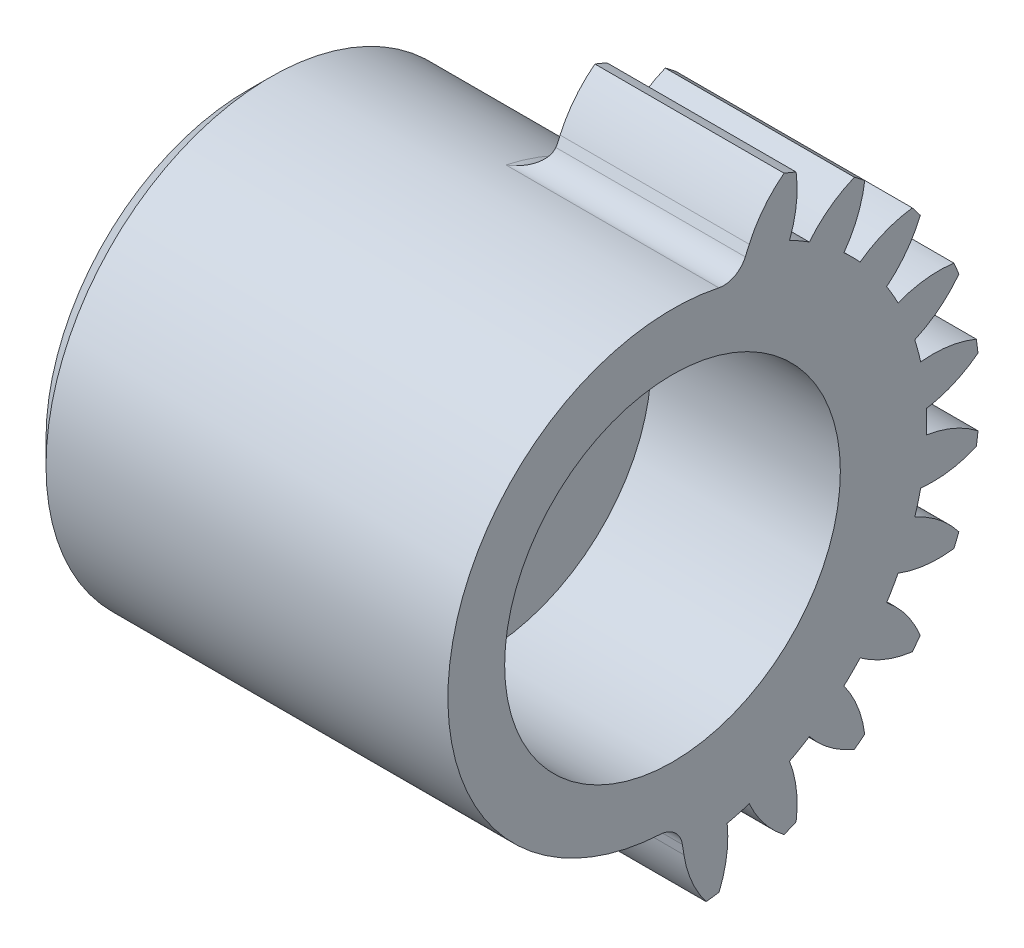
SolidWorks part; units mm, degrees
ref_plane "Plane1" through (0, 0, 0) normal (0, 0, 1) x (1, 0, 0)
ref_plane "Plane2" through (0, 0, 0) normal (0, 1, 0) x (1, 0, 0)
ref_plane "Plane3" through (0, 0, 0) normal (1, 0, 0) x (0, 0, -1)
sketch "HoldingSke" plane through (0, 0, 0) normal (0, 1, 0) x (1, 0, 0)
  line L0 (0, 0) -> (0.9135, -0.4067)
  line L1 (-15, 0) -> (100, 0) construction
  line L2 (0, 0) -> (-2.1039, 2.3779)
  line L3 (0, 0) -> (-11.863, 4.5341)
  line L4 (0, 0) -> (7.8894, 3.5126)
  line L5 (0, 0) -> (-46.8476, -17.4728)
  line L6 (0, 0) -> (-6.6317, -4.4744)
  line L7 (-2.1039, 2.3779) -> (8.6586, 51.2059)
  line L8 (-76.2, 54.61) -> (-75.3, 54.61)
  line L9 (-71.009, 38.7566) -> (-53.1078, 45.2721)
  line L10 (-76.2, 71.12) -> (104.1128, 71.12)
  line L11 (0, 0) -> (-8, 0)
  line L12 (-76.2, 101.6) -> (-76.162, 101.6)
  line L13 (24.9733, 27.94) -> (52.9518, 28.4284)
  line L14 (24.9733, 27.94) -> (24.9743, 27.94)
  line L15 (24.9733, 27.94) -> (100.4006, 29.5858)
  line L16 (-63.627, -1) -> (-12.827, -1)
  circle A0 centre (0, 0) radius 2.5
  circle A1 centre (0, 0) radius 10.749
  circle A2 centre (0, 0) radius 37.5
  circle A3 centre (0, 0) radius 2.5
  dimension "Num_teeth" = 24
  dimension "Pitch_radius" = 180.3128
  dimension "Width" = 8
  dimension "Thickness" = 8
sketch "BasProSke" plane through (0, 0, 0) normal (0, 1, 0) x (1, 0, 0)
  line L0 (-10, 0) -> (60, 0) construction
  line L1 (0, 0) -> (0, 13)
  line L2 (0, 0) -> (8, 0)
  line L3 (8, 0) -> (8, 13)
  line L4 (8, 13) -> (0, 13)
  dimension "Thickness" = 8
  dimension "Diameter" = 26
revolve "Base-Revolve" add sketch "BasProSke" angle 360 about L0
sketch "TooCutSke" plane through (0, 0, 0) normal (1, 0, 0) x (0, 0, -1)
  line L1 (0, 0) -> (0, 107) construction
  line L2 (0, 0) -> (-0.8513, 11.9698) construction
  line L3 (0, 0) -> (-3.127, 23.752) construction
  line L4 (-0.8513, 11.9698) -> (-1.5635, 11.876) construction
  arc A0 (0.4834, 10.7381) -> (-0.4834, 10.7381) centre (0, 0) ccw
  arc A1 (1.4409, 12.9455) -> (-1.4409, 12.9455) centre (0, 0) ccw
  circle A2 centre (0, 0) radius 12 construction
  circle A3 centre (0, 0) radius 11.2763 construction
  arc A4 (-0.4834, 10.7381) -> (-1.4409, 12.9455) centre (-5.2252, 9.9926) ccw
  arc A5 (1.4409, 12.9455) -> (0.4834, 10.7381) centre (5.2252, 9.9926) ccw
extrude "ToothCut" cut sketch "TooCutSke" along normal through all
fillet "Breaks" [suppressed] radius 0.02 tangent propagation no
fillet "RootFillets" [suppressed] radius 0.251
pattern_circular "TeethCuts" count 24 every 15 about axis through (-10, 0, 0) along (1, 0, 0) of "ToothCut", "RootFillets", "Breaks"
sketch "HubNeaOneSke" plane through (0, 0, 0) normal (-1, 0, 0) x (0, 0, 1)
  circle A0 centre (0, 0) radius 10.749
  dimension "Diameter" = 21.498
extrude "HubNearOne" [suppressed] add sketch "HubNeaOneSke" along normal blind 42.0001
sketch "HubNeaBotSke" plane through (0, 0, 0) normal (-1, 0, 0) x (0, 0, 1)
  circle A0 centre (0, 0) radius 10.749
  dimension "Diameter" = 21.498
extrude "HubNearBoth" [suppressed] add sketch "HubNeaBotSke" along normal blind 21
ref_plane "FarPln" through (8, 0, 0) normal (1, 0, 0) x (0, 0, -1)
sketch "HubFarSke" plane through (8, 0, 0) normal (1, 0, 0) x (0, 0, -1)
  circle A0 centre (0, 0) radius 10.749
  dimension "Diameter" = 21.498
extrude "HubFar" [suppressed] add sketch "HubFarSke" along normal blind 21
sketch "BorSke" plane through (0, 0, 0) normal (1, 0, 0) x (0, 0, -1)
  circle A0 centre (0, 0) radius 2.5
  dimension "Diameter" = 5
extrude "Bore" cut sketch "BorSke" along normal mid plane 100.0001
sketch "KeySke" plane through (0, 0, 0) normal (1, 0, 0) x (0, 0, -1)
  line L0 (-1, 0) -> (-1, 3.4)
  line L1 (-1, 3.4) -> (1, 3.4)
  line L2 (1, 3.4) -> (1, 0)
  line L3 (0, 0) -> (0, 34) construction
  line L4 (-1, 0) -> (1, 0)
  dimension "Width" = 2
extrude "Keyway" [suppressed] cut sketch "KeySke" along normal mid plane 100.0001
pattern_circular "Keyway2" [suppressed] count 2 every 90 about axis through (-10, 0, 0) along (1, 0, 0)
sketch "Sketch2" plane through (0, 0, 0) normal (-1, 0, 0) x (0, 0, 1)
  line L0 (-3.2462, 10.2471) -> (-2.7359, 9.0975)
  line L1 (-0.4834, -10.7381) -> (-0.2881, -9.4956)
  circle A0 centre (0, 0) radius 2.5 construction
  circle A1 centre (0, 0) radius 2.5
  circle A2 centre (0, 0) radius 9.5
  circle A3 centre (0, 0) radius 7.1
  arc A100 (10.7381, 0.4834) -> (12.9219, 1.4227) centre (9.9926, 5.2252) ccw
  arc A101 (12.9219, 1.4227) -> (12.8498, 1.9702) centre (0, 0) ccw
  arc A102 (12.8498, 1.9702) -> (10.4974, 2.3123) centre (11.0045, -2.4609) ccw
  arc A103 (10.4974, 2.3123) -> (10.2471, 3.2462) centre (0, 0) ccw
  arc A104 (10.2471, 3.2462) -> (12.1134, 4.7186) centre (8.2997, 7.6334) ccw
  arc A105 (12.1134, 4.7186) -> (11.902, 5.2289) centre (0, 0) ccw
  arc A106 (11.902, 5.2289) -> (9.5412, 4.9504) centre (11.2665, 0.4712) ccw
  arc A107 (9.5412, 4.9504) -> (9.0578, 5.7877) centre (0, 0) ccw
  arc A108 (9.0578, 5.7877) -> (10.4794, 7.693) centre (6.0413, 9.5215) ccw
  arc A109 (10.4794, 7.693) -> (10.1432, 8.1312) centre (0, 0) ccw
  arc A110 (10.1432, 8.1312) -> (7.9348, 7.2511) centre (10.7606, 3.3711) ccw
  arc A111 (7.9348, 7.2511) -> (7.2511, 7.9348) centre (0, 0) ccw
  arc A112 (7.2511, 7.9348) -> (8.1312, 10.1432) centre (3.3711, 10.7606) ccw
  arc A113 (8.1312, 10.1432) -> (7.693, 10.4794) centre (0, 0) ccw
  arc A114 (7.693, 10.4794) -> (5.7877, 9.0578) centre (9.5215, 6.0413) ccw
  arc A115 (5.7877, 9.0578) -> (4.9504, 9.5412) centre (0, 0) ccw
  arc A116 (4.9504, 9.5412) -> (5.2289, 11.902) centre (0.4712, 11.2665) ccw
  arc A117 (5.2289, 11.902) -> (4.7186, 12.1134) centre (0, 0) ccw
  arc A118 (4.7186, 12.1134) -> (3.2462, 10.2471) centre (7.6334, 8.2997) ccw
  arc A119 (3.2462, 10.2471) -> (2.3123, 10.4974) centre (0, 0) ccw
  arc A120 (2.3123, 10.4974) -> (1.9702, 12.8498) centre (-2.4609, 11.0045) ccw
  arc A121 (1.9702, 12.8498) -> (1.4227, 12.9219) centre (0, 0) ccw
  arc A122 (1.4227, 12.9219) -> (0.4834, 10.7381) centre (5.2252, 9.9926) ccw
  arc A123 (0.4834, 10.7381) -> (-0.4834, 10.7381) centre (0, 0) ccw
  arc A124 (-0.4834, 10.7381) -> (-1.4227, 12.9219) centre (-5.2252, 9.9926) ccw
  arc A125 (-1.4227, 12.9219) -> (-1.9702, 12.8498) centre (0, 0) ccw
  arc A126 (-1.9702, 12.8498) -> (-2.3123, 10.4974) centre (2.4609, 11.0045) ccw
  arc A127 (-2.3123, 10.4974) -> (-3.2462, 10.2471) centre (0, 0) ccw
  arc A128 (-3.2462, 10.2471) -> (-4.7186, 12.1134) centre (-7.6334, 8.2997) ccw
  arc A129 (-4.7186, 12.1134) -> (-5.2289, 11.902) centre (0, 0) ccw
  arc A130 (-5.2289, 11.902) -> (-4.9504, 9.5412) centre (-0.4712, 11.2665) ccw
  arc A131 (-4.9504, 9.5412) -> (-5.7877, 9.0578) centre (0, 0) ccw
  arc A132 (-5.7877, 9.0578) -> (-7.693, 10.4794) centre (-9.5215, 6.0413) ccw
  arc A133 (-7.693, 10.4794) -> (-8.1312, 10.1432) centre (0, 0) ccw
  arc A134 (-8.1312, 10.1432) -> (-7.2511, 7.9348) centre (-3.3711, 10.7606) ccw
  arc A135 (-7.2511, 7.9348) -> (-7.9348, 7.2511) centre (0, 0) ccw
  arc A136 (-7.9348, 7.2511) -> (-10.1432, 8.1312) centre (-10.7606, 3.3711) ccw
  arc A137 (-10.1432, 8.1312) -> (-10.4794, 7.693) centre (0, 0) ccw
  arc A138 (-10.4794, 7.693) -> (-9.0578, 5.7877) centre (-6.0413, 9.5215) ccw
  arc A139 (-9.0578, 5.7877) -> (-9.5412, 4.9504) centre (0, 0) ccw
  arc A140 (-9.5412, 4.9504) -> (-11.902, 5.2289) centre (-11.2665, 0.4712) ccw
  arc A141 (-11.902, 5.2289) -> (-12.1134, 4.7186) centre (0, 0) ccw
  arc A142 (-12.1134, 4.7186) -> (-10.2471, 3.2462) centre (-8.2997, 7.6334) ccw
  arc A143 (-10.2471, 3.2462) -> (-10.4974, 2.3123) centre (0, 0) ccw
  arc A144 (-10.4974, 2.3123) -> (-12.8498, 1.9702) centre (-11.0045, -2.4609) ccw
  arc A145 (-12.8498, 1.9702) -> (-12.9219, 1.4227) centre (0, 0) ccw
  arc A146 (-12.9219, 1.4227) -> (-10.7381, 0.4834) centre (-9.9926, 5.2252) ccw
  arc A147 (-10.7381, 0.4834) -> (-10.7381, -0.4834) centre (0, 0) ccw
  arc A148 (-10.7381, -0.4834) -> (-12.9219, -1.4227) centre (-9.9926, -5.2252) ccw
  arc A149 (-12.9219, -1.4227) -> (-12.8498, -1.9702) centre (0, 0) ccw
  arc A150 (-12.8498, -1.9702) -> (-10.4974, -2.3123) centre (-11.0045, 2.4609) ccw
  arc A151 (-10.4974, -2.3123) -> (-10.2471, -3.2462) centre (0, 0) ccw
  arc A152 (-10.2471, -3.2462) -> (-12.1134, -4.7186) centre (-8.2997, -7.6334) ccw
  arc A153 (-12.1134, -4.7186) -> (-11.902, -5.2289) centre (0, 0) ccw
  arc A154 (-11.902, -5.2289) -> (-9.5412, -4.9504) centre (-11.2665, -0.4712) ccw
  arc A155 (-9.5412, -4.9504) -> (-9.0578, -5.7877) centre (0, 0) ccw
  arc A156 (-9.0578, -5.7877) -> (-10.4794, -7.693) centre (-6.0413, -9.5215) ccw
  arc A157 (-10.4794, -7.693) -> (-10.1432, -8.1312) centre (0, 0) ccw
  arc A158 (-10.1432, -8.1312) -> (-7.9348, -7.2511) centre (-10.7606, -3.3711) ccw
  arc A159 (-7.9348, -7.2511) -> (-7.2511, -7.9348) centre (0, 0) ccw
  arc A160 (-7.2511, -7.9348) -> (-8.1312, -10.1432) centre (-3.3711, -10.7606) ccw
  arc A161 (-8.1312, -10.1432) -> (-7.693, -10.4794) centre (0, 0) ccw
  arc A162 (-7.693, -10.4794) -> (-5.7877, -9.0578) centre (-9.5215, -6.0413) ccw
  arc A163 (-5.7877, -9.0578) -> (-4.9504, -9.5412) centre (0, 0) ccw
  arc A164 (-4.9504, -9.5412) -> (-5.2289, -11.902) centre (-0.4712, -11.2665) ccw
  arc A165 (-5.2289, -11.902) -> (-4.7186, -12.1134) centre (0, 0) ccw
  arc A166 (-4.7186, -12.1134) -> (-3.2462, -10.2471) centre (-7.6334, -8.2997) ccw
  arc A167 (-3.2462, -10.2471) -> (-2.3123, -10.4974) centre (0, 0) ccw
  arc A168 (-2.3123, -10.4974) -> (-1.9702, -12.8498) centre (2.4609, -11.0045) ccw
  arc A169 (-1.9702, -12.8498) -> (-1.4227, -12.9219) centre (0, 0) ccw
  arc A170 (-1.4227, -12.9219) -> (-0.4834, -10.7381) centre (-5.2252, -9.9926) ccw
  arc A171 (-0.4834, -10.7381) -> (0.4834, -10.7381) centre (0, 0) ccw
  arc A172 (0.4834, -10.7381) -> (1.4227, -12.9219) centre (5.2252, -9.9926) ccw
  arc A173 (1.4227, -12.9219) -> (1.9702, -12.8498) centre (0, 0) ccw
  arc A174 (1.9702, -12.8498) -> (2.3123, -10.4974) centre (-2.4609, -11.0045) ccw
  arc A175 (2.3123, -10.4974) -> (3.2462, -10.2471) centre (0, 0) ccw
  arc A176 (3.2462, -10.2471) -> (4.7186, -12.1134) centre (7.6334, -8.2997) ccw
  arc A177 (4.7186, -12.1134) -> (5.2289, -11.902) centre (0, 0) ccw
  arc A178 (5.2289, -11.902) -> (4.9504, -9.5412) centre (0.4712, -11.2665) ccw
  arc A179 (4.9504, -9.5412) -> (5.7877, -9.0578) centre (0, 0) ccw
  arc A180 (5.7877, -9.0578) -> (7.693, -10.4794) centre (9.5215, -6.0413) ccw
  arc A181 (7.693, -10.4794) -> (8.1312, -10.1432) centre (0, 0) ccw
  arc A182 (8.1312, -10.1432) -> (7.2511, -7.9348) centre (3.3711, -10.7606) ccw
  arc A183 (7.2511, -7.9348) -> (7.9348, -7.2511) centre (0, 0) ccw
  arc A184 (7.9348, -7.2511) -> (10.1432, -8.1312) centre (10.7606, -3.3711) ccw
  arc A185 (10.1432, -8.1312) -> (10.4794, -7.693) centre (0, 0) ccw
  arc A186 (10.4794, -7.693) -> (9.0578, -5.7877) centre (6.0413, -9.5215) ccw
  arc A187 (9.0578, -5.7877) -> (9.5412, -4.9504) centre (0, 0) ccw
  arc A188 (9.5412, -4.9504) -> (11.902, -5.2289) centre (11.2665, -0.4712) ccw
  arc A189 (11.902, -5.2289) -> (12.1134, -4.7186) centre (0, 0) ccw
  arc A190 (12.1134, -4.7186) -> (10.2471, -3.2462) centre (8.2997, -7.6334) ccw
  arc A191 (10.2471, -3.2462) -> (10.4974, -2.3123) centre (0, 0) ccw
  arc A192 (10.4974, -2.3123) -> (12.8498, -1.9702) centre (11.0045, 2.4609) ccw
  arc A193 (12.8498, -1.9702) -> (12.9219, -1.4227) centre (0, 0) ccw
  arc A194 (12.9219, -1.4227) -> (10.7381, -0.4834) centre (9.9926, -5.2252) ccw
  arc A195 (10.7381, -0.4834) -> (10.7381, 0.4834) centre (0, 0) ccw
  arc A196 (10.7381, 0.4834) -> (12.9219, 1.4227) centre (9.9926, 5.2252) ccw
  arc A197 (12.9219, 1.4227) -> (12.8498, 1.9702) centre (0, 0) ccw
  arc A198 (12.8498, 1.9702) -> (10.4974, 2.3123) centre (11.0045, -2.4609) ccw
  arc A199 (10.4974, 2.3123) -> (10.2471, 3.2462) centre (0, 0) ccw
  arc A200 (10.2471, 3.2462) -> (12.1134, 4.7186) centre (8.2997, 7.6334) ccw
  arc A201 (12.1134, 4.7186) -> (11.902, 5.2289) centre (0, 0) ccw
  arc A202 (11.902, 5.2289) -> (9.5412, 4.9504) centre (11.2665, 0.4712) ccw
  arc A203 (9.5412, 4.9504) -> (9.0578, 5.7877) centre (0, 0) ccw
  arc A204 (9.0578, 5.7877) -> (10.4794, 7.693) centre (6.0413, 9.5215) ccw
  arc A205 (10.4794, 7.693) -> (10.1432, 8.1312) centre (0, 0) ccw
  arc A206 (10.1432, 8.1312) -> (7.9348, 7.2511) centre (10.7606, 3.3711) ccw
  arc A207 (7.9348, 7.2511) -> (7.2511, 7.9348) centre (0, 0) ccw
  arc A208 (7.2511, 7.9348) -> (8.1312, 10.1432) centre (3.3711, 10.7606) ccw
  arc A209 (8.1312, 10.1432) -> (7.693, 10.4794) centre (0, 0) ccw
  arc A210 (7.693, 10.4794) -> (5.7877, 9.0578) centre (9.5215, 6.0413) ccw
  arc A211 (5.7877, 9.0578) -> (4.9504, 9.5412) centre (0, 0) ccw
  arc A212 (4.9504, 9.5412) -> (5.2289, 11.902) centre (0.4712, 11.2665) ccw
  arc A213 (5.2289, 11.902) -> (4.7186, 12.1134) centre (0, 0) ccw
  arc A214 (4.7186, 12.1134) -> (3.2462, 10.2471) centre (7.6334, 8.2997) ccw
  arc A215 (3.2462, 10.2471) -> (2.3123, 10.4974) centre (0, 0) ccw
  arc A216 (2.3123, 10.4974) -> (1.9702, 12.8498) centre (-2.4609, 11.0045) ccw
  arc A217 (1.9702, 12.8498) -> (1.4227, 12.9219) centre (0, 0) ccw
  arc A218 (1.4227, 12.9219) -> (0.4834, 10.7381) centre (5.2252, 9.9926) ccw
  arc A219 (0.4834, 10.7381) -> (-0.4834, 10.7381) centre (0, 0) ccw
  arc A220 (-0.4834, 10.7381) -> (-1.4227, 12.9219) centre (-5.2252, 9.9926) ccw
  arc A221 (-1.4227, 12.9219) -> (-1.9702, 12.8498) centre (0, 0) ccw
  arc A222 (-1.9702, 12.8498) -> (-2.3123, 10.4974) centre (2.4609, 11.0045) ccw
  arc A223 (-2.3123, 10.4974) -> (-3.2462, 10.2471) centre (0, 0) ccw
  arc A224 (-3.2462, 10.2471) -> (-4.7186, 12.1134) centre (-7.6334, 8.2997) ccw
  arc A225 (-4.7186, 12.1134) -> (-5.2289, 11.902) centre (0, 0) ccw
  arc A226 (-5.2289, 11.902) -> (-4.9504, 9.5412) centre (-0.4712, 11.2665) ccw
  arc A227 (-4.9504, 9.5412) -> (-5.7877, 9.0578) centre (0, 0) ccw
  arc A228 (-5.7877, 9.0578) -> (-7.693, 10.4794) centre (-9.5215, 6.0413) ccw
  arc A229 (-7.693, 10.4794) -> (-8.1312, 10.1432) centre (0, 0) ccw
  arc A230 (-8.1312, 10.1432) -> (-7.2511, 7.9348) centre (-3.3711, 10.7606) ccw
  arc A231 (-7.2511, 7.9348) -> (-7.9348, 7.2511) centre (0, 0) ccw
  arc A232 (-7.9348, 7.2511) -> (-10.1432, 8.1312) centre (-10.7606, 3.3711) ccw
  arc A233 (-10.1432, 8.1312) -> (-10.4794, 7.693) centre (0, 0) ccw
  arc A234 (-10.4794, 7.693) -> (-9.0578, 5.7877) centre (-6.0413, 9.5215) ccw
  arc A235 (-9.0578, 5.7877) -> (-9.5412, 4.9504) centre (0, 0) ccw
  arc A236 (-9.5412, 4.9504) -> (-11.902, 5.2289) centre (-11.2665, 0.4712) ccw
  arc A237 (-11.902, 5.2289) -> (-12.1134, 4.7186) centre (0, 0) ccw
  arc A238 (-12.1134, 4.7186) -> (-10.2471, 3.2462) centre (-8.2997, 7.6334) ccw
  arc A239 (-10.2471, 3.2462) -> (-10.4974, 2.3123) centre (0, 0) ccw
  arc A240 (-10.4974, 2.3123) -> (-12.8498, 1.9702) centre (-11.0045, -2.4609) ccw
  arc A241 (-12.8498, 1.9702) -> (-12.9219, 1.4227) centre (0, 0) ccw
  arc A242 (-12.9219, 1.4227) -> (-10.7381, 0.4834) centre (-9.9926, 5.2252) ccw
  arc A243 (-10.7381, 0.4834) -> (-10.7381, -0.4834) centre (0, 0) ccw
  arc A244 (-10.7381, -0.4834) -> (-12.9219, -1.4227) centre (-9.9926, -5.2252) ccw
  arc A245 (-12.9219, -1.4227) -> (-12.8498, -1.9702) centre (0, 0) ccw
  arc A246 (-12.8498, -1.9702) -> (-10.4974, -2.3123) centre (-11.0045, 2.4609) ccw
  arc A247 (-10.4974, -2.3123) -> (-10.2471, -3.2462) centre (0, 0) ccw
  arc A248 (-10.2471, -3.2462) -> (-12.1134, -4.7186) centre (-8.2997, -7.6334) ccw
  arc A249 (-12.1134, -4.7186) -> (-11.902, -5.2289) centre (0, 0) ccw
  arc A250 (-11.902, -5.2289) -> (-9.5412, -4.9504) centre (-11.2665, -0.4712) ccw
  arc A251 (-9.5412, -4.9504) -> (-9.0578, -5.7877) centre (0, 0) ccw
  arc A252 (-9.0578, -5.7877) -> (-10.4794, -7.693) centre (-6.0413, -9.5215) ccw
  arc A253 (-10.4794, -7.693) -> (-10.1432, -8.1312) centre (0, 0) ccw
  arc A254 (-10.1432, -8.1312) -> (-7.9348, -7.2511) centre (-10.7606, -3.3711) ccw
  arc A255 (-7.9348, -7.2511) -> (-7.2511, -7.9348) centre (0, 0) ccw
  arc A256 (-7.2511, -7.9348) -> (-8.1312, -10.1432) centre (-3.3711, -10.7606) ccw
  arc A257 (-8.1312, -10.1432) -> (-7.693, -10.4794) centre (0, 0) ccw
  arc A258 (-7.693, -10.4794) -> (-5.7877, -9.0578) centre (-9.5215, -6.0413) ccw
  arc A259 (-5.7877, -9.0578) -> (-4.9504, -9.5412) centre (0, 0) ccw
  arc A260 (-4.9504, -9.5412) -> (-5.2289, -11.902) centre (-0.4712, -11.2665) ccw
  arc A261 (-5.2289, -11.902) -> (-4.7186, -12.1134) centre (0, 0) ccw
  arc A262 (-4.7186, -12.1134) -> (-3.2462, -10.2471) centre (-7.6334, -8.2997) ccw
  arc A263 (-3.2462, -10.2471) -> (-2.3123, -10.4974) centre (0, 0) ccw
  arc A264 (-2.3123, -10.4974) -> (-1.9702, -12.8498) centre (2.4609, -11.0045) ccw
  arc A265 (-1.9702, -12.8498) -> (-1.4227, -12.9219) centre (0, 0) ccw
  arc A266 (-1.4227, -12.9219) -> (-0.4834, -10.7381) centre (-5.2252, -9.9926) ccw
  arc A267 (-0.4834, -10.7381) -> (0.4834, -10.7381) centre (0, 0) ccw
  arc A268 (0.4834, -10.7381) -> (1.4227, -12.9219) centre (5.2252, -9.9926) ccw
  arc A269 (1.4227, -12.9219) -> (1.9702, -12.8498) centre (0, 0) ccw
  arc A270 (1.9702, -12.8498) -> (2.3123, -10.4974) centre (-2.4609, -11.0045) ccw
  arc A271 (2.3123, -10.4974) -> (3.2462, -10.2471) centre (0, 0) ccw
  arc A272 (3.2462, -10.2471) -> (4.7186, -12.1134) centre (7.6334, -8.2997) ccw
  arc A273 (4.7186, -12.1134) -> (5.2289, -11.902) centre (0, 0) ccw
  arc A274 (5.2289, -11.902) -> (4.9504, -9.5412) centre (0.4712, -11.2665) ccw
  arc A275 (4.9504, -9.5412) -> (5.7877, -9.0578) centre (0, 0) ccw
  arc A276 (5.7877, -9.0578) -> (7.693, -10.4794) centre (9.5215, -6.0413) ccw
  arc A277 (7.693, -10.4794) -> (8.1312, -10.1432) centre (0, 0) ccw
  arc A278 (8.1312, -10.1432) -> (7.2511, -7.9348) centre (3.3711, -10.7606) ccw
  arc A279 (7.2511, -7.9348) -> (7.9348, -7.2511) centre (0, 0) ccw
  arc A280 (7.9348, -7.2511) -> (10.1432, -8.1312) centre (10.7606, -3.3711) ccw
  arc A281 (10.1432, -8.1312) -> (10.4794, -7.693) centre (0, 0) ccw
  arc A282 (10.4794, -7.693) -> (9.0578, -5.7877) centre (6.0413, -9.5215) ccw
  arc A283 (9.0578, -5.7877) -> (9.5412, -4.9504) centre (0, 0) ccw
  arc A284 (9.5412, -4.9504) -> (11.902, -5.2289) centre (11.2665, -0.4712) ccw
  arc A285 (11.902, -5.2289) -> (12.1134, -4.7186) centre (0, 0) ccw
  arc A286 (12.1134, -4.7186) -> (10.2471, -3.2462) centre (8.2997, -7.6334) ccw
  arc A287 (10.2471, -3.2462) -> (10.4974, -2.3123) centre (0, 0) ccw
  arc A288 (10.4974, -2.3123) -> (12.8498, -1.9702) centre (11.0045, 2.4609) ccw
  arc A289 (12.8498, -1.9702) -> (12.9219, -1.4227) centre (0, 0) ccw
  arc A290 (12.9219, -1.4227) -> (10.7381, -0.4834) centre (9.9926, -5.2252) ccw
  arc A291 (10.7381, -0.4834) -> (10.7381, 0.4834) centre (0, 0) ccw
  dimension "D1" = 19
  dimension "D2" = 14.2
  dimension "D3" = 0
extrude "Boss-Extrude1" add sketch "Sketch2" along normal blind 10 contours A3 A1 | A2 A3 region at (0, 7.4081, 5.5079) region at (0, 0, -6.8992)
extrude "Cut-Extrude1" cut sketch "Sketch2<3>" against normal blind 10 contours A290 A291 A196 A197 A198 A199 A200 A201 A202 A203 A204 A205 A206 A207 A208 A209 A210 A211 A212 A213 A214 A215 A216 A217 A218 A219 A220 A221 A222 A223 L0 A2 L1 A267 A268 A269 A270 A271 A272 A273 A274 A275 A276 A277 A278 A279 A280 A281 A282 A283 A284 region at (0, 10.0883, -2.7031)
sketch "Sketch2<3>" plane through (0, 0, 0) normal (-1, 0, 0) x (0, 0, 1) same geometry as "Sketch2"
extrude "Cut-Extrude2" cut sketch "Sketch2<4>" against normal through all contours A3 A1 region at (0, 0, -6.8992)
sketch "Sketch2<4>" plane through (0, 0, 0) normal (-1, 0, 0) x (0, 0, 1) same geometry as "Sketch2"
fillet "Fillet1" radius 1 3 edges at (4, -9.4956, -0.2881) (4, 9.0975, -2.7359) (0, -1.24, -9.4187)
chamfer "Chamfer1" distance 1 angle 45 2 edges at (-10, 0, 9.5) (-10, 0, 2.5)
equation "' \"Module@HoldingSke\" = 6.35"
equation "' \"Num_teeth@HoldingSke\" = 12"
equation "' \"Ap@HoldingSke\" =  20"
equation "' \"Ap@HoldingSke\" = 20"
equation "' \"Width@HoldingSke\" = 0.5 * 25.4"
equation "' \"Hub_dia@HoldingSke\"= 1 * 25.4"
equation "' \"Hub_dia@HoldingSke\" = 1 * 25.4"
equation "' \"Overall_len@HoldingSke\" = 1.0 * 25.4"
equation "' \"Bore@HoldingSke\" = 0.75 * 25.4"
equation "' \"T_dim@HoldingSke\" = 0.1 * 25.4"
equation "' \"Width@KeySke\" = 0.25 * 25.4"
equation "' \"Show_teeth@HoldingSke\" = 13"
equation "' \"Backlash@HoldingSke\" = 0.009 * 25.4"
equation "' \"Addendum_fac@HoldingSke\" = 1.0"
equation "' \"Dedendum_fac@HoldingSke\" = 1.25"
equation "' \"Dedendum_add@HoldingSke\" = 0.00005 * 25.4"
equation "' \"Clearance_fac@HoldingSke\" = 0.25"
equation "\"Pitch@HoldingSke\" = 1 / \"Module@HoldingSke\""
equation "\"Overcut_dia@TooCutSke\" = (\"Num_teeth@HoldingSke\" + 2 * \"Addendum_fac@HoldingSke\") / \"Pitch@HoldingSke\" + 0.002 * 25.4"
equation "\"Pitch_dia@TooCutSke\" = \"Num_teeth@HoldingSke\" / \"Pitch@HoldingSke\""
equation "\"Base_dia@TooCutSke\" = \"Num_teeth@HoldingSke\" / \"Pitch@HoldingSke\" * cos((\"Ap@HoldingSke\"  * 3.14159265 / 180))"
equation "\"Root_dia@TooCutSke\" = (\"Num_teeth@HoldingSke\" + 2) / \"Pitch@HoldingSke\" - 2 * (\"Addendum_fac@HoldingSke\" + \"Dedendum_fac@HoldingSke\") / \"Pitch@HoldingSke\" - \"Dedendum_add@HoldingSke\" * 2"
equation "\"Half_ang@TooCutSke\" = 180 / \"Num_teeth@HoldingSke\""
equation "\"Half_CT@TooCutSke\" = \"Num_teeth@HoldingSke\" / \"Pitch@HoldingSke\" * sin((3.14159265 / 2 / \"Num_teeth@HoldingSke\")) / 2 - 7 * \"Backlash@HoldingSke\" / 4"
equation "\"Flank_rad@TooCutSke\" = \"Num_teeth@HoldingSke\" / \"Pitch@HoldingSke\" / 5"
equation "\"Radius@RootFillets\" = \"Clearance_fac@HoldingSke\" / \"Pitch@HoldingSke\" + \"Dedendum_add@HoldingSke\""
equation "\"Break_rad@Breaks\" = 0.02 / \"Pitch@HoldingSke\""
equation "\"Thickness@HoldingSke\" = \"Width@HoldingSke\""
equation "\"OAL@HoldingSke\" = \"Thickness@HoldingSke\""
equation "\"MHD@HoldingSke\" = (\"Num_teeth@HoldingSke\" + 2) / \"Pitch@HoldingSke\" - 2 * (\"Addendum_fac@HoldingSke\" + \"Dedendum_fac@HoldingSke\")  / \"Pitch@HoldingSke\" - \"Dedendum_add@HoldingSke\" * 2"
equation "\"MBD@HoldingSke\" = (\"Num_teeth@HoldingSke\" + 2) / \"Pitch@HoldingSke\" - 2 * (\"Addendum_fac@HoldingSke\" + \"Dedendum_fac@HoldingSke\")  / \"Pitch@HoldingSke\" - \"Dedendum_add@HoldingSke\" * 2 - 0.002 * 25.4"
equation "\"MHD@HoldingSke\" = ((sgn( \"MHD@HoldingSke\" - \"Hub_dia@HoldingSke\" )-1)*( \"MHD@HoldingSke\" - \"Hub_dia@HoldingSke\" ))/-2+ \"Hub_dia@HoldingSke\""
equation "\"MBD@HoldingSke\" = ((sgn( \"MBD@HoldingSke\" - \"Bore@HoldingSke\" )-1)*( \"MBD@HoldingSke\" - \"Bore@HoldingSke\" ))/-2+ \"Bore@HoldingSke\""
equation "\"OAL@HoldingSke\" = ((sgn( \"OAL@HoldingSke\" - \"Overall_len@HoldingSke\" )+1)*( \"OAL@HoldingSke\" - \"Overall_len@HoldingSke\" ))/2 + \"Overall_len@HoldingSke\" + 0.000002 * 25.4"
equation "\"Num_teeth@TeethCuts\" = int( \"Show_teeth@HoldingSke\" ) + 1"
equation "\"Num_teeth@TeethCuts\" = ((sgn( \"Num_teeth@TeethCuts\" - \"Num_teeth@HoldingSke\" )-1)*( \"Num_teeth@TeethCuts\" - \"Num_teeth@HoldingSke\" ))/-2+ \"Num_teeth@HoldingSke\""
equation "\"Num_teeth@TeethCuts\" = ((sgn( \"Num_teeth@TeethCuts\" - 2.0)+1)*( \"Num_teeth@TeethCuts\" - 2.0))/2 +2.0"
equation "\"Angle@TeethCuts\" = 360.0 / \"Num_teeth@HoldingSke\""
equation "\"Diameter@BasProSke\" = (\"Num_teeth@HoldingSke\" + 2 * \"Addendum_fac@HoldingSke\") / \"Pitch@HoldingSke\""
equation "\"Thickness@BasProSke\"  = \"Thickness@HoldingSke\""
equation "' \"Fillet_rad@BasProSke\" =  \"Thickness@HoldingSke\" * 0.05"
equation "' \"Fillet_rad@BasProSke\" = \"Thickness@HoldingSke\" * 0.05"
equation "\"MHD@HoldingSke\" = ((sgn( \"MHD@HoldingSke\" - \"Root_dia@TooCutSke\" )-1)*( \"MHD@HoldingSke\" - \"Root_dia@TooCutSke\" ))/-2+ \"Root_dia@TooCutSke\""
equation "\"Diameter@HubNeaOneSke\" = \"MHD@HoldingSke\""
equation "\"Length@HubNearOne\" = \"OAL@HoldingSke\" - \"Thickness@BasProSke\""
equation "\"Diameter@HubNeaBotSke\" = \"MHD@HoldingSke\""
equation "\"Length@HubNearBoth\" = ( \"OAL@HoldingSke\" - \"Thickness@BasProSke\" ) / 2.0"
equation "\"Thickness@FarPln\" = \"Thickness@BasProSke\""
equation "\"Diameter@HubFarSke\" = \"MHD@HoldingSke\""
equation "\"Length@HubFar\" = ( \"OAL@HoldingSke\" - \"Thickness@BasProSke\" ) / 2.0"
equation "\"Diameter@BorSke\" = \"MBD@HoldingSke\""
equation "\"D1@Bore\" = \"OAL@HoldingSke\" * 2.0"
equation "\"D1@Keyway\" = \"OAL@HoldingSke\" * 2.0"
equation "\"Offset@KeySke\" = \"T_dim@HoldingSke\" + \"MBD@HoldingSke\" / 2.0"
